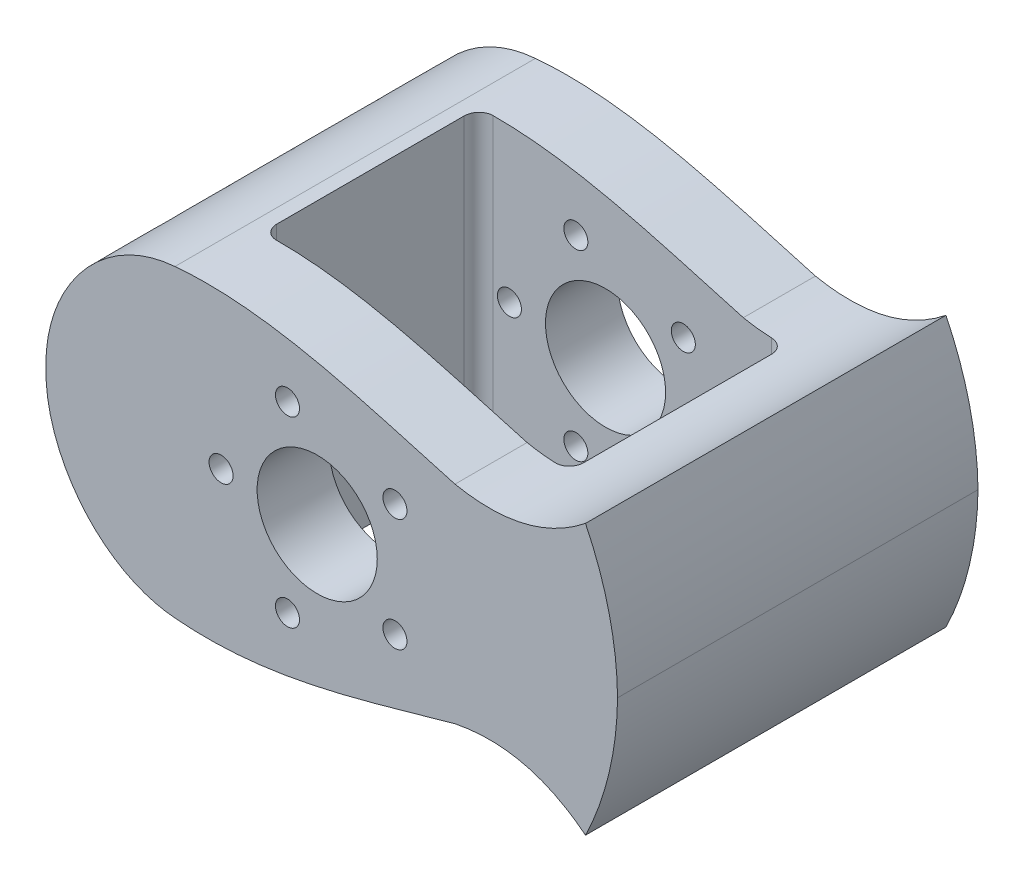
SolidWorks part; units mm, degrees
material "AISI 4340 Aço, normalizado"
ref_plane "Plano frontal" through (0, 0, 0) normal (0, 0, 1) x (1, 0, 0)
ref_plane "Plano superior" through (0, 0, 0) normal (0, 1, 0) x (1, 0, 0)
ref_plane "Plano direito" through (0, 0, 0) normal (1, 0, 0) x (0, 0, -1)
sketch "Esboço1" plane through (0, 0, 0) normal (0, 0, 1) x (1, 0, 0)
  line L0 (-62.5, 0) -> (62.5, 0) construction
  circle A0 centre (0, 0) radius 62.5 construction
  arc A1 (55.8293, 28.0951) -> (62.5, 0) centre (-2.934, -0.6966) cw
  arc A2 (55.8293, -28.0951) -> (62.5, 0) centre (-2.934, 0.6966) ccw
  spline S0 degree 3 poles (-56.4301, 0) (-56.8049, 15.0574) (-45.2002, 30.4123) (-29.5944, 31.6766) knots 0 0 0 0 1 1 1 1
  spline S1 degree 2 poles (28.6769, 21.5883) (43.8615, 18.534) (55.8293, 28.0951) knots 0 0 0 1 1 1
  spline S2 degree 3 poles (-29.5944, 31.6766) (-9.7242, 33.4395) (9.8731, 26.7709) (28.6769, 21.5883) knots 0 0 0 0 1 1 1 1
  spline S3 degree 2 poles (28.6769, -21.5883) (43.8615, -18.534) (55.8293, -28.0951) knots 0 0 0 1 1 1
  spline S4 degree 3 poles (-29.5944, -31.6766) (-9.7242, -33.4395) (9.8731, -26.7709) (28.6769, -21.5883) knots 0 0 0 0 1 1 1 1
  spline S5 degree 3 poles (-56.4301, 0) (-56.8049, -15.0574) (-45.2002, -30.4123) (-29.5944, -31.6766) knots 0 0 0 0 1 1 1 1
  dimension "D1" = 125
  dimension "D2" = 59.4912
  dimension "D3" = 45.5105
  dimension "D4" = 28.9021
  dimension "D5" = 65.4377
  dimension "D15" = 58.2713
  dimension "D6" = 28.0951
  dimension "D7" = 21.9018
  dimension "D8" = 21.5883
  dimension "D9" = 28.713
  dimension "D10" = 31.8589
  dimension "D11" = 31.6766
  dimension "D12" = 26.52
  dimension "D13" = 13.7052
  dimension "D14" = 56.4301
  dimension "D16" = 27.1524
  dimension "D17" = 13.6094
  dimension "D18" = 10.8623
extrude "Ressalto-extrusão1" add sketch "Esboço1" along normal blind 75
sketch "Esboço2" plane through (0, 0, 0) normal (0, 1, 0) x (1, 0, 0)
  line L0 (-26.4301, -15) -> (37.5, -15)
  line L1 (37.5, -15) -> (37.5, -60)
  line L2 (37.5, -60) -> (-26.4301, -60)
  line L3 (-26.4301, -60) -> (-26.4301, -15)
  line L4 (-29.5944, 0) -> (-56.4389, 0) construction
  line L5 (-56.4389, -75) -> (-29.5944, -75) construction
  line L8 (62.5, -75) -> (62.5, 0) construction
  line L9 (-56.4301, -75) -> (-56.4301, 0) construction
  dimension "D1" = 15
  dimension "D2" = 15
  dimension "D3" = 25
  dimension "D4" = 30
extrude "Corte-extrusão1" cut sketch "Esboço2" against normal blind 70 and the other way blind 70
sketch "Esboço3" plane through (0, 0, 75) normal (0, 0, 1) x (1, 0, 0)
  circle A0 centre (0, 0) radius 12.5
  dimension "D1" = 25
extrude "Corte-extrusão2" cut sketch "Esboço3" against normal through all
fillet "Filete1" radius 3 4 edges at (37.5, 0, 60) (37.5, 0, 15) (-26.4301, 0, 60) (-26.4301, 0, 15)
hole_wizard "Broca de rosquear para tarraxa de M61" positions "Esboço4" profile "Esboço5" hole size "M6" standard "ISO" end condition through all
sketch "Esboço4" plane through (0, 0, 75) normal (0, 0, 1) x (1, 0, 0)
  line L0 (0, 0) -> (-6.1803, 19.0211) construction
  line L1 (0, 0) -> (-20, 0) construction
  line L2 (-6.1803, -19.0211) -> (0, 0) construction
  line L3 (0, 0) -> (16.1803, -11.7557) construction
  line L5 (0, 0) -> (16.1803, 11.7557) construction
  point P0 (-6.1803, 19.0211)
  point P15 (16.1803, 11.7557)
  point P16 (16.1803, -11.7557)
  point P17 (-6.1803, -19.0211)
  point P18 (-20, 0)
  dimension "D1" = 20
  dimension "D3" = 72
  dimension "D4" = 72
  dimension "D5" = 72
  dimension "D6" = 72
  dimension "D7" = 72
  dimension "D2" = 5
sketch "Esboço5" plane through (-6.1803, 19.0211, 75) normal (1, 0, 0) x (0, -1, 0)
  line L0 (0, 0) -> (0, 75)
  line L1 (0, 75) -> (2.5, 75)
  line L2 (2.5, 75) -> (2.5, 0)
  line L5 (2.5, 0) -> (0, 0)
  line L11 (0, -6.35) -> (0, 107.95) construction
  dimension "Thru Hole Dia." = 5
  dimension "Thru Hole Depth" = 75
